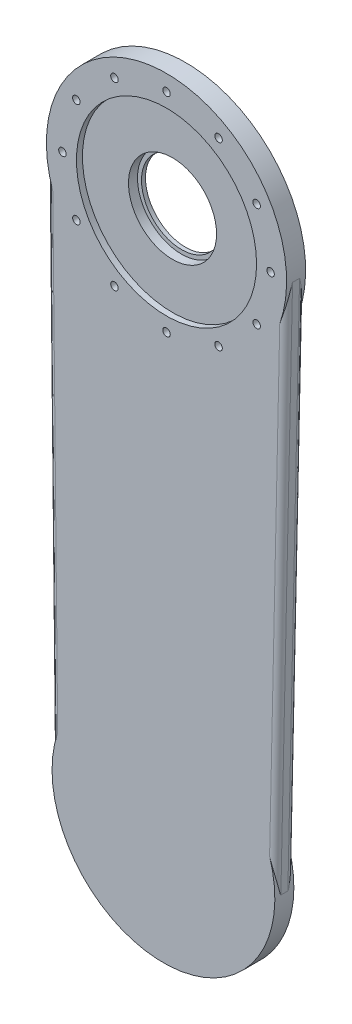
SolidWorks part; units mm, degrees
ref_plane "Front Plane" through (0, 0, 0) normal (0, 0, 1) x (1, 0, 0)
ref_plane "Top Plane" through (0, 0, 0) normal (0, 1, 0) x (1, 0, 0)
ref_plane "Right Plane" through (0, 0, 0) normal (1, 0, 0) x (0, 0, -1)
sketch "Sketch1" plane through (0, 0, 0) normal (0, 0, 1) x (1, 0, 0)
  circle A0 centre (0, 0) radius 60
extrude "Boss-Extrude1" add sketch "Sketch1" along normal blind 9.5
sketch "Sketch7" plane through (0, 0, 9.5) normal (0, 0, 1) x (1, 0, 0)
  circle A1 centre (0, 0) radius 22
  point P14 (0, 0)
  dimension "D1" = 44
extrude "Cut-Extrude6" cut sketch "Sketch7" against normal blind 30 contours A1
sketch "Sketch9" plane through (0, 0, 9.5) normal (0, 0, 1) x (1, 0, 0)
  line L1 (-60, 0) -> (-57.1783, -269.9361)
  line L3 (54.1281, -269.9361) -> (59.9961, -0.6802)
  arc A1 (-57.1783, -269.9361) -> (54.1281, -269.9361) centre (-1.5251, -269.9361) ccw
  circle A2 centre (0, 0) radius 60 construction
  arc A4 (-59.9934, -0.6271) -> (59.9825, -1.3072) centre (0, 0) ccw
extrude "Boss-Extrude3" add sketch "Sketch9" against normal blind 9.5
fillet "Fillet3" radius 3 1 edges at (57.0485, -135.9352, 0)
fillet "Fillet5" radius 3 1 edges at (57.0485, -135.9352, 9.5)
sketch "Sketch11" plane through (0, 0, 9.5) normal (0, 0, 1) x (1, 0, 0)
  circle A0 centre (0, 0) radius 45
sketch "Sketch12" plane through (0, 0, 9.5) normal (0, 0, 1) x (1, 0, 0)
  circle A1 centre (26, -45.0333) radius 1.875
  circle A2 centre (-26, -45.0333) radius 1.875
  circle A3 centre (-52, 0) radius 1.875
  circle A4 centre (-26, 45.0333) radius 1.875
  circle A5 centre (26, 45.0333) radius 1.875
  circle A6 centre (52, 0) radius 1.875
  circle A7 centre (-45.0333, 26) radius 1.875
  circle A8 centre (-26, 45.0333) radius 1.875
  circle A9 centre (0, 52) radius 1.875
  circle A10 centre (26, 45.0333) radius 1.875
  circle A11 centre (45.0333, 26) radius 1.875
  circle A12 centre (52, 0) radius 1.875
  circle A13 centre (45.0333, -26) radius 1.875
  circle A14 centre (26, -45.0333) radius 1.875
  circle A15 centre (0, -52) radius 1.875
  circle A16 centre (-26, -45.0333) radius 1.875
  circle A17 centre (-45.0333, -26) radius 1.875
  circle A18 centre (0, 0) radius 52 construction
  point P18 (0, 0)
  point P41 (0, 0)
  dimension "D1" = 6
  dimension "D3" = 104
  dimension "D2" = 12
extrude "Cut-Extrude12" cut sketch "Sketch12" against normal blind 30
extrude "Cut-Extrude13" cut sketch "Sketch11" against normal blind 3
fillet "Fillet6" radius 3 1 edges at (-58.5826, -135.5952, 9.5)
sketch "Sketch13" plane through (0, 0, 0) normal (0, 0, -1) x (-1, 0, 0)
  circle A0 centre (0, 0) radius 22
extrude "Boss-Extrude4" add sketch "Sketch13" against normal blind 2
sketch "Sketch14" plane through (0, 0, 0) normal (0, 0, -1) x (-1, 0, 0)
  circle A0 centre (0, 0) radius 20
  dimension "D1" = 40
extrude "Cut-Extrude14" cut sketch "Sketch14" against normal blind 2
